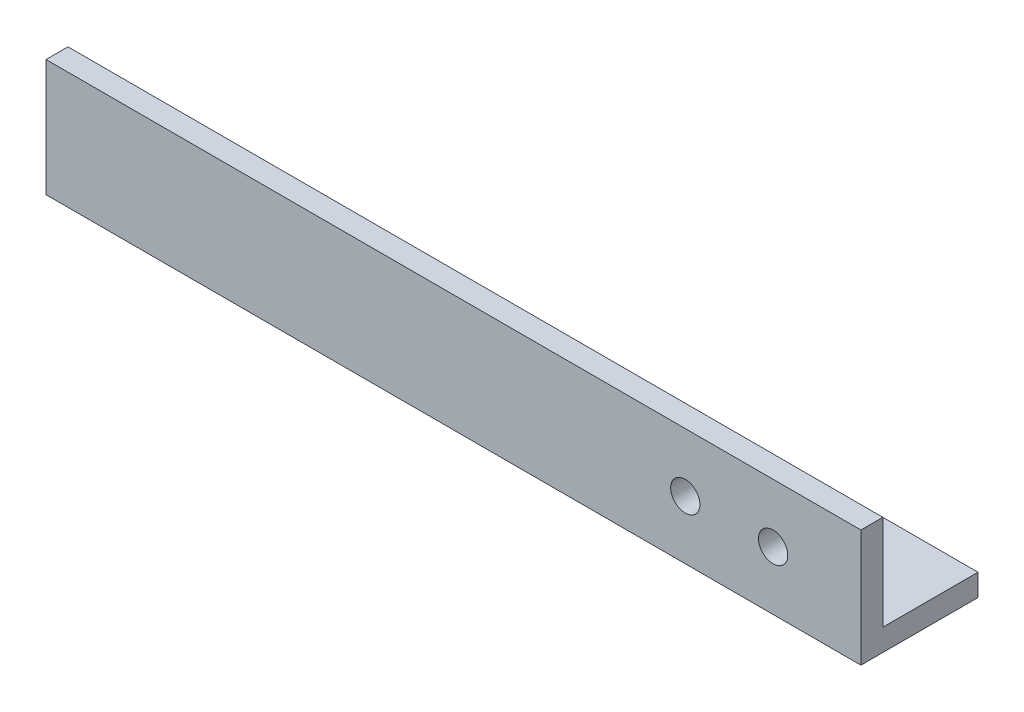
SolidWorks part; units mm, degrees
material "6061 Alloy"
ref_plane "Front Plane" through (0, 0, 0) normal (0, 0, 1) x (1, 0, 0)
ref_plane "Top Plane" through (0, 0, 0) normal (0, 1, 0) x (1, 0, 0)
ref_plane "Right Plane" through (0, 0, 0) normal (1, 0, 0) x (0, 0, -1)
sketch "Sketch1" plane through (0, 0, 0) normal (1, 0, 0) x (0, 0, -1)
  line L0 (0, 0) -> (0, -25.4)
  line L1 (0, -25.4) -> (25.4, -25.4)
  line L2 (25.4, -25.4) -> (25.4, -20.6375)
  line L3 (25.4, -20.6375) -> (4.7625, -20.6375)
  line L4 (4.7625, -20.6375) -> (4.7625, 0)
  line L5 (4.7625, 0) -> (0, 0)
  dimension "D1" = 4.7625
  dimension "D2" = 4.7625
  dimension "D3" = 25.4
  dimension "D4" = 25.4
extrude "Boss-Extrude1" add sketch "Sketch1" along normal blind 176.784
sketch "Sketch2" plane through (0, -20.6375, 0) normal (0, 1, 0) x (1, 0, 0)
  line L1 (0, 25.4) -> (0, 4.7625) construction
  line L2 (176.784, 0) -> (0, 0) construction
  circle A0 centre (9.525, 11.1125) radius 3.175
  circle A1 centre (19.05, 17.4625) radius 3.175
  dimension "D1" = 11.1125
  dimension "D2" = 17.4625
  dimension "D3" = 19.05
  dimension "D4" = 6.35
  dimension "D5" = 6.35
  dimension "D6" = 9.525
extrude "Cut-Extrude1" cut sketch "Sketch2" against normal up to next
sketch "Sketch3" plane through (0, -25.4, 0) normal (0, -1, 0) x (1, 0, 0)
  circle A0 centre (112.2532, -13.4704) radius 3.175 construction
  circle A1 centre (112.2532, -13.4704) radius 3.175
extrude "Cut-Extrude2" cut sketch "Sketch3" against normal up to next
sketch "Sketch6" plane through (0, 0, 0) normal (0, 0, 1) x (1, 0, 0)
  circle A0 centre (138.684, -12.7) radius 3.175 construction
  circle A1 centre (157.734, -12.7) radius 3.175 construction
  circle A2 centre (138.684, -12.7) radius 3.175
  circle A3 centre (157.734, -12.7) radius 3.175
extrude "Cut-Extrude3" cut sketch "Sketch6" against normal up to next
